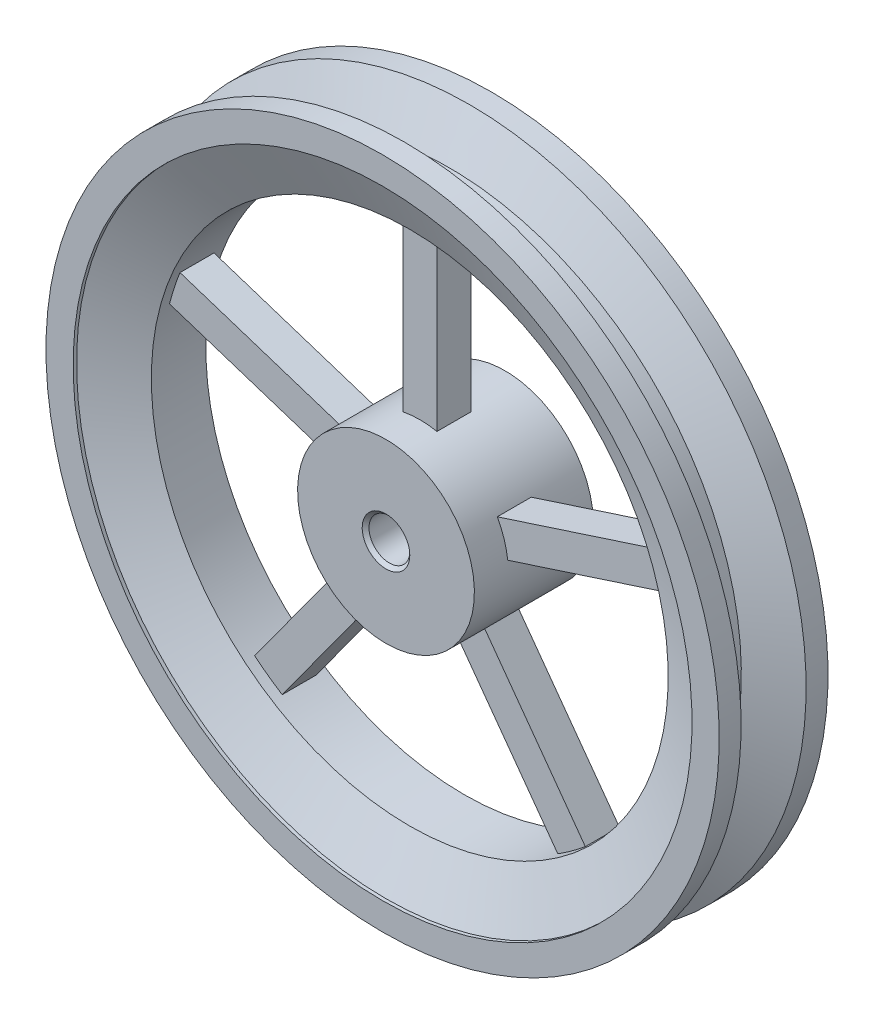
SolidWorks part; units mm, degrees
ref_plane "Alzado" through (0, 0, 0) normal (0, 0, 1) x (1, 0, 0)
ref_plane "Planta" through (0, 0, 0) normal (0, 1, 0) x (1, 0, 0)
ref_plane "Vista lateral" through (0, 0, 0) normal (1, 0, 0) x (0, 0, -1)
sketch "Croquis2" plane through (0, 0, 0) normal (1, 0, 0) x (0, 0, -1)
  line L0 (0, 0) -> (0, 186) construction
  line L1 (-7, 160) -> (7, 160)
  line L2 (7, 160) -> (19.124, 186)
  line L3 (19.124, 186) -> (32, 186)
  line L4 (32, 186) -> (32, 170)
  line L5 (32, 170) -> (30, 170)
  line L6 (30, 170) -> (16.0108, 140)
  line L7 (16.0108, 140) -> (10, 140)
  line L8 (10, 140) -> (10, 40)
  line L9 (10, 40) -> (40, 40)
  line L10 (40, 40) -> (40, 0)
  line L11 (40, 0) -> (0, 0)
  line L12 (-16.0108, 140) -> (-10, 140)
  line L13 (-10, 140) -> (-10, 40)
  line L14 (-19.124, 186) -> (-32, 186)
  line L15 (-32, 186) -> (-32, 170)
  line L16 (-32, 170) -> (-30, 170)
  line L17 (-30, 170) -> (-16.0108, 140)
  line L18 (-7, 160) -> (-19.124, 186)
  line L19 (-10, 40) -> (-30, 40)
  line L20 (-30, 40) -> (-30, 0)
  line L21 (-30, 0) -> (0, 0)
  line L22 (-30, -12) -> (40, -12) construction
  point P22 (0, 160)
  point P25 (40, 20)
  point P29 (-30, 20)
  dimension "D1" = 100
  dimension "D2" = 120
  dimension "D3" = 130
  dimension "D4" = 146
  dimension "D5" = 25
  dimension "D6" = 7
  dimension "D7" = 32
  dimension "D8" = 10
  dimension "D9" = 40
  dimension "D10" = 40
  dimension "D11" = 70
  dimension "D12" = 12
revolve "Revolución1" add sketch "Croquis2" angle 360 about L22
sketch "Croquis3" plane through (0, 0, 10) normal (0, 0, 1) x (1, 0, 0)
  line L0 (51.622, -5.7416) -> (147.3376, 25.3583)
  line L2 (-10, 39.0294) -> (-10, 139.6707)
  line L4 (10, 39.0294) -> (10, 139.6707)
  line L5 (45.4417, 13.2795) -> (141.1572, 44.3794)
  line L6 (21.9042, -59.1615) -> (81.0596, -140.582)
  line L7 (38.0845, -47.4058) -> (97.24, -128.8263)
  line L8 (-38.0845, -47.4058) -> (-97.24, -128.8263)
  line L9 (-21.9042, -59.1615) -> (-81.0596, -140.582)
  line L10 (-45.4417, 13.2795) -> (-141.1572, 44.3794)
  line L11 (-51.622, -5.7416) -> (-147.3376, 25.3583)
  circle A0 centre (0, -12) radius 52 construction
  circle A1 centre (0, -12) radius 152 construction
  circle A2 centre (0, -12) radius 52
  circle A3 centre (0, -12) radius 152
  point P29 (0, -12)
  circle M1 centre (0, -12) radius 52
  circle M2 centre (0, -12) radius 152
  dimension "D1" = 20
  dimension "D2" = 5
extrude "Cortar-Extruir1" cut sketch "Croquis3" against normal blind 20 contours L11 L8 M1 M2 | L10 L2 M1 M2 | L5 L4 M1 M2 | L7 L0 M1 M2 | L9 L6 M1 M2 region at (101.152, -44.8663, 10) region at (62.5154, 74.0451, 10) region at (0, -118.3576, 10) region at (-62.5154, 74.0451, 10) region at (-101.152, -44.8663, 10)
chamfer "Chaflán1" distance 2 angle 45 2 edges at (0, -24, -40) (0, -24, 30)
